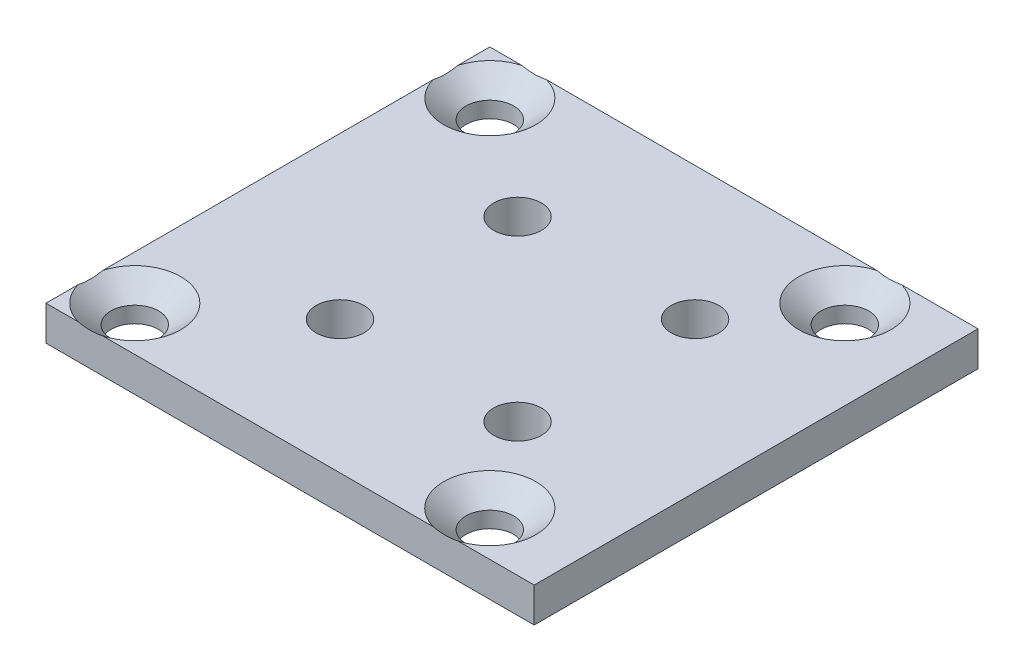
SolidWorks part; units mm, degrees
note: '?' marks a value the reader was unsure of.
material "6061 Alloy"
ref_plane "Front Plane" through (0, 0, 0) normal (0, 0, 1) x (1, 0, 0)
ref_plane "Top Plane" through (0, 0, 0) normal (0, 1, 0) x (1, 0, 0)
ref_plane "Right Plane" through (0, 0, 0) normal (1, 0, 0) x (0, 0, -1)
sketch "Sketch1" plane through (0, 0, 0) normal (0, 1, 0) x (1, 0, 0)
  line L1 (-21.5, -20) -> (21.5, -20)
  line L2 (-21.5, -20) -> (-21.5, 20)
  line L3 (-21.5, 20) -> (21.5, 20)
  line L4 (21.5, -20) -> (21.5, 20)
  line L5 (-21.5, -20) -> (21.5, 20) construction
  line L6 (-21.5, 20) -> (21.5, -20) construction
  point P0 (0, 0)
  dimension "D1" = 43
  dimension "D2" = 40
extrude "Boss-Extrude1" add sketch "Sketch1" along normal blind 3.125
sketch "Sketch2" plane through (0, 3.125, 0) normal (0, 1, 0) x (1, 0, 0)
  line L0 (21.5, 20) -> (-21.5, 20) construction
  line L1 (-21.5, 20) -> (-21.5, -20) construction
  point P0 (-18.5, 16)
  point P8 (-2.5, 16)
  point P9 (13.5, 16)
  point P10 (-2.5, -16)
  point P11 (13.5, -16)
  point P12 (-18.5, -16)
  dimension "D1" = 4
  dimension "D2" = 3
  dimension "D5" = 32
  dimension "D6" = 16
  dimension "D3" = 3
  dimension "D4" = 2
hole_wizard "M4 Clearance Hole1" positions "Sketch2" profile "Sketch3" hole size "M4" standard "ANSI Metric"
sketch "Sketch3" plane through (-18.5, 3.125, -16) normal (1, 0, 0) x (0, 0, 1)
  line L0 (0, 0) -> (0, 3.125)
  line L1 (0, 3.125) -> (2.15, 3.125)
  line L2 (2.15, 3.125) -> (2.15, 0)
  line L5 (2.15, 0) -> (0, 0)
  line L11 (0, -6.35) -> (0, 107.95) construction
  dimension "Thru Hole Dia." = 4.3
  dimension "Thru Hole Depth" = 3.125
sketch "Sketch5" plane through (0, 3.125, 0) normal (0, 1, 0) x (1, 0, 0)
  point P0 (-8, 8)
  point P5 (8, 8)
  point P6 (8, -8)
  point P7 (-8, -8)
  dimension "D1" = 8
  dimension "D2" = 8
  dimension "D4" = 16
  dimension "D3" = 4
hole_wizard "M4 Clearance Hole2" positions "Sketch5" profile "Sketch6" hole size "M4" standard "ANSI Metric" end condition through all
sketch "Sketch6" plane through (-8, 3.125, -8) normal (1, 0, 0) x (0, 0, 1)
  line L0 (0, 0) -> (0, 3.125)
  line L1 (0, 3.125) -> (2.15, 3.125)
  line L2 (2.15, 3.125) -> (2.15, 0)
  line L5 (2.15, 0) -> (0, 0)
  line L11 (0, -6.35) -> (0, 107.95) construction
  dimension "Thru Hole Dia." = 4.3
  dimension "Thru Hole Depth" = 3.125
sketch "Sketch7" plane through (-21.5, 0, 0) normal (-1, 0, 0) x (0, 0, 1)
  line L1 (-20, 0) -> (20, 0)
  line L2 (-20, 0) -> (-20, 3.125)
  line L3 (-20, 3.125) -> (20, 3.125)
  line L4 (20, 0) -> (20, 3.125)
extrude "Boss-Extrude2" add sketch "Sketch7" along normal blind 1
chamfer "Chamfer1" distance 2 angle 40 4 edges at (-18.5, 3.125, 18.15) (-18.5, 3.125, -13.85) (13.5, 3.125, 18.15) (13.5, 3.125, -13.85)
sketch "Sketch8" plane through (0, 3.125, 0) normal (0, 1, 0) x (1, 0, 0)
  point P0 (0, 0)
ref_axis "Axis1" through (0, -20.1816, 0) along (0, 1, 0)?
